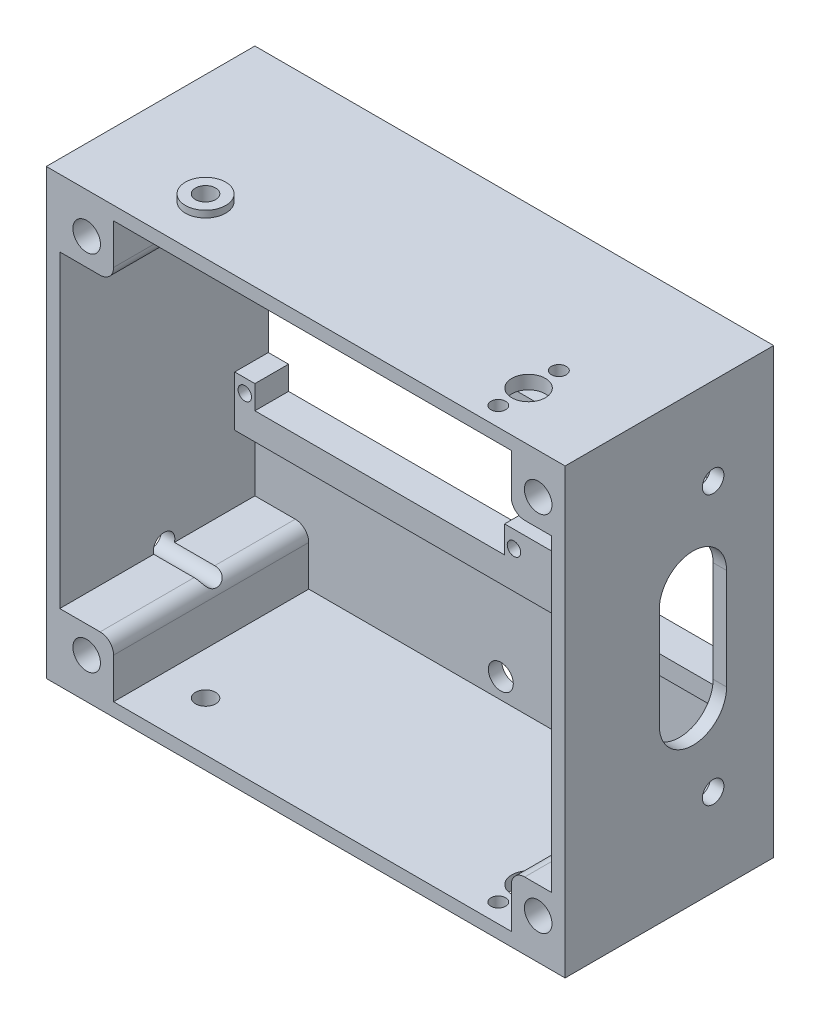
SolidWorks part; units mm, degrees
material "PET"
ref_plane "Спереди" through (0, 0, 0) normal (0, 0, 1) x (1, 0, 0)
ref_plane "Сверху" through (0, 0, 0) normal (0, 1, 0) x (1, 0, 0)
ref_plane "Справа" through (0, 0, 0) normal (1, 0, 0) x (0, 0, -1)
sketch "Эскиз1" plane through (0, 0, 0) normal (0, 0, 1) x (1, 0, 0)
  line L0 (-36.55, 30.95) -> (36.55, -30.95) construction
  line L1 (-36.55, -30.95) -> (36.55, -30.95)
  line L2 (-36.55, -30.95) -> (-36.55, 30.95)
  line L3 (-36.55, 30.95) -> (36.55, 30.95)
  line L4 (36.55, -30.95) -> (36.55, 30.95)
  line L8 (-38.55, -32.95) -> (38.55, -32.95)
  line L9 (38.55, -32.95) -> (38.55, 32.95)
  line L10 (-38.55, 32.95) -> (38.55, 32.95)
  line L11 (-38.55, -32.95) -> (-38.55, 32.95)
  point P0 (0, 0)
  dimension "D1" = 61.9
  dimension "D2" = 73.1
  dimension "D3" = 2
extrude "Бобышка-Вытянуть1" add sketch "Эскиз1" along normal blind 31
sketch "Эскиз2" plane through (0, 0, 0) normal (0, 0, -1) x (-1, 0, 0)
  line L12 (38.55, -32.95) -> (38.55, 32.95)
  line L13 (38.55, 32.95) -> (-38.55, 32.95)
  line L14 (-38.55, 32.95) -> (-38.55, -32.95)
  line L15 (-38.55, -32.95) -> (38.55, -32.95)
  line L16 (38.55, -32.95) -> (38.55, 32.95)
  line L17 (38.55, 32.95) -> (-38.55, 32.95)
  line L18 (-38.55, 32.95) -> (-38.55, -32.95)
  line L19 (-38.55, -32.95) -> (38.55, -32.95)
  dimension "D1" = 0
extrude "Бобышка-Вытянуть2" add sketch "Эскиз2" against normal blind 2
sketch "Эскиз3" plane through (0, -32.95, 0) normal (0, -1, 0) x (1, 0, 0)
  line L0 (25.8041, 19.187) -> (25.8041, 28.187) construction
  line L1 (24.9041, 19.187) -> (26.7041, 19.187) construction
  circle A0 centre (25.8041, 23.687) radius 2.5
  circle A1 centre (25.8041, 19.187) radius 1.1
  circle A2 centre (25.8041, 28.187) radius 1.1
  point P6 (25.8041, 23.687)
  dimension "D1" = 5
  dimension "D2" = 2.2
extrude "Вырез-Вытянуть1" cut sketch "Эскиз3" against normal through all both and the other way through all
sketch "Эскиз4" plane through (0, 0, 2) normal (0, 0, 1) x (1, 0, 0)
  line L0 (-36.55, 30.95) -> (-36.55, -30.95) construction
  line L1 (-36.55, -9) -> (-36.55, 9)
  line L2 (-36.55, -9) -> (13.45, -9)
  line L3 (-36.55, 9) -> (13.45, 9)
  line L4 (13.45, -9) -> (13.45, 9) construction
  line L5 (13.45, -10.2) -> (13.45, 10.2) construction
  line L6 (13.45, -10.2) -> (35.35, -10.2)
  line L7 (13.45, 10.2) -> (35.35, 10.2)
  line L8 (35.35, -10.2) -> (35.35, 10.2)
  line L9 (13.45, -10.2) -> (13.45, -9)
  line L10 (13.45, 10.2) -> (13.45, 9)
  line L11 (36.55, -30.95) -> (36.55, 30.95) construction
  circle A0 centre (0, 27.94) radius 1.651 construction
  circle A1 centre (0, -27.94) radius 1.651 construction
  circle A2 centre (0, 27.94) radius 1.651 construction
  circle A3 centre (0, -27.94) radius 1.651 construction
  circle A4 centre (0, 27.94) radius 1.851
  circle A5 centre (0, -27.94) radius 1.851
  point P10 (-36.55, 0)
  point P11 (13.45, 0)
  dimension "D2" = 50
  dimension "D3" = 18
  dimension "D4" = 1.2
  dimension "D5" = 1.2
  dimension "D1" = 0.2
extrude "Вырез-Вытянуть2" cut sketch "Эскиз4" against normal through all both and the other way through all
sketch "Эскиз5" plane through (0, 0, 2) normal (0, 0, 1) x (1, 0, 0)
  line L0 (16.3959, -10.2) -> (16.3959, 10.2)
  line L1 (16.3959, -10.2) -> (7.557, -10.2)
  line L2 (16.3959, 10.2) -> (7.557, 10.2)
  line L3 (7.557, -10.2) -> (7.557, 10.2)
  line L4 (35.35, -10.2) -> (13.45, -10.2) construction
  line L5 (13.45, 10.2) -> (35.35, 10.2) construction
  line L7 (17.0959, -7.9497) -> (17.0959, -9.7292) construction
  line L8 (7.357, -8.8303) -> (7.357, -6.3963) construction
  line L9 (-36.55, -9) -> (-33.55, -9)
  line L10 (-36.55, -9) -> (-36.55, -5.5)
  line L11 (-33.55, -9) -> (-33.55, -5.5)
  line L12 (-36.55, -5.5) -> (-33.55, -5.5)
  line L13 (13.45, -9) -> (-36.55, -9) construction
  line L14 (-36.55, 9) -> (-33.55, 9)
  line L15 (-36.55, 9) -> (-36.55, 5.5)
  line L16 (-33.55, 9) -> (-33.55, 5.5)
  line L17 (-36.55, 5.5) -> (-33.55, 5.5)
  line L18 (-36.55, 9) -> (13.45, 9) construction
  dimension "D1" = 0.7
  dimension "D2" = 0.2
  dimension "D3" = 3.5
  dimension "D4" = 3
extrude "Бобышка-Вытянуть3" add sketch "Эскиз5" against normal up to surface (2 mm away) up to face at (1.851, 27.94, 0)
sketch "Эскиз7" plane through (0, 0, 2) normal (0, 0, 1) x (1, 0, 0)
  line L0 (7.557, -5) -> (7.557, 5)
  line L1 (7.557, -5) -> (12.557, -5)
  line L2 (7.557, 5) -> (12.557, 5)
  line L3 (12.557, -5) -> (12.557, 5)
  line L4 (7.557, 9) -> (7.557, -9) construction
  point P6 (7.557, 0)
  dimension "D1" = 10
  dimension "D2" = 5
extrude "Вырез-Вытянуть3" cut sketch "Эскиз7" against normal through all both and the other way through all
sketch "Эскиз9" plane through (0, 0, 2) normal (0, 0, 1) x (1, 0, 0)
  line L20 (-36.55, 13) -> (36.55, 13)
  line L25 (-36.55, -13) -> (36.55, -13)
  line L38 (16.3959, 10.2) -> (16.3959, -10.2)
  line L39 (35.35, 10.2) -> (16.3959, 10.2)
  line L40 (35.35, -10.2) -> (35.35, 10.2)
  line L41 (16.3959, -10.2) -> (35.35, -10.2)
  line L58 (16.3959, 10.2) -> (16.3959, -10.2)
  line L59 (35.35, 10.2) -> (16.3959, 10.2)
  line L60 (35.35, -10.2) -> (35.35, 10.2)
  line L61 (16.3959, -10.2) -> (35.35, -10.2)
  line L64 (12.557, 5) -> (12.557, -5)
  line L65 (12.557, -5) -> (7.557, -5)
  line L66 (7.557, -5) -> (7.557, -9)
  line L72 (7.557, -9) -> (-33.55, -9)
  line L73 (-33.55, -9) -> (-33.55, -5.5)
  line L74 (-33.55, -5.5) -> (-36.55, -5.5)
  line L75 (-36.55, -5.5) -> (-36.55, -30.95)
  line L76 (-36.55, -30.95) -> (36.55, -30.95)
  line L80 (36.55, -30.95) -> (36.55, 30.95)
  line L98 (36.55, 30.95) -> (-36.55, 30.95)
  line L99 (-36.55, 30.95) -> (-36.55, 5.5)
  line L100 (-36.55, 5.5) -> (-33.55, 5.5)
  line L101 (-33.55, 5.5) -> (-33.55, 9)
  line L102 (-33.55, 9) -> (7.557, 9)
  line L103 (7.557, 9) -> (7.557, 5)
  line L104 (7.557, 5) -> (12.557, 5)
  line L105 (12.557, 5) -> (12.557, -5)
  line L106 (12.557, -5) -> (7.557, -5)
  line L107 (7.557, -5) -> (7.557, -9)
  line L108 (7.557, -9) -> (-33.55, -9)
  line L109 (-33.55, -9) -> (-33.55, -5.5)
  line L110 (-33.55, -5.5) -> (-36.55, -5.5)
  line L111 (-36.55, -5.5) -> (-36.55, -13)
  line L113 (36.55, -13) -> (36.55, 13)
  line L115 (-36.55, 13) -> (-36.55, 5.5)
  line L116 (-36.55, 5.5) -> (-33.55, 5.5)
  line L117 (-33.55, 5.5) -> (-33.55, 9)
  line L118 (-33.55, 9) -> (7.557, 9)
  line L119 (7.557, 9) -> (7.557, 5)
  line L120 (7.557, 5) -> (12.557, 5)
  dimension "D1" = 0
  dimension "D2" = 4
  dimension "D5" = 0
extrude "Бобышка-Вытянуть4" add sketch "Эскиз9" along normal up to surface (3 mm away)
sketch "Эскиз11" plane through (12.557, 0, 0) normal (-1, 0, 0) x (0, 0, 1)
  line L12 (5, 5) -> (0, 5)
  line L13 (0, 5) -> (0, -5)
  line L14 (0, -5) -> (5, -5)
  line L15 (5, -5) -> (5, 5)
  line L16 (5, 5) -> (0, 5)
  line L17 (0, 5) -> (0, -5)
  line L18 (0, -5) -> (5, -5)
  line L19 (5, -5) -> (5, 5)
  dimension "D1" = 0
extrude "Вырез-Вытянуть4" cut sketch "Эскиз11" against normal up to surface (3.8389 mm away) up to face at (16.3959, 0, 2.5)
sketch "Эскиз27" plane through (7.557, 0, 0) normal (-1, 0, 0) x (0, 0, 1)
  line L0 (5, -5) -> (0, -5) construction
  line L1 (0, -5) -> (0, -9) construction
  line L2 (0, -9) -> (5, -9) construction
  line L3 (5, -9) -> (5, -5) construction
  line L4 (0, 5) -> (5, 5) construction
  line L5 (5, 5) -> (5, 9) construction
  line L6 (5, 9) -> (0, 9) construction
  line L7 (0, 9) -> (0, 5) construction
  line L8 (5, -5) -> (0, -5)
  line L9 (0, -5) -> (0, -9)
  line L10 (0, -9) -> (5, -9)
  line L11 (5, -9) -> (5, -5)
  line L12 (0, 5) -> (5, 5)
  line L13 (5, 5) -> (5, 9)
  line L14 (5, 9) -> (0, 9)
  line L15 (0, 9) -> (0, 5)
extrude "Бобышка-Вытянуть12" add sketch "Эскиз27" along normal blind 5
sketch "Эскиз13" plane through (0, 0, 5) normal (0, 0, 1) x (1, 0, 0)
  line L0 (-35.05, 7.5) -> (-35.05, -7.5) construction
  line L1 (-35.05, 7.5) -> (4.95, 7.5) construction
  line L2 (-35.05, -7.5) -> (4.95, -7.5) construction
  line L3 (4.95, 7.5) -> (4.95, -7.5) construction
  line L4 (-35.05, 0) -> (-36.55, 0) construction
  line L5 (-36.55, 30.95) -> (-36.55, -30.95) construction
  circle A4 centre (-35.05, 7.5) radius 1
  circle A5 centre (-35.05, -7.5) radius 1
  circle A6 centre (4.95, -7.5) radius 1
  circle A7 centre (4.95, 7.5) radius 1
  point P0 (-35.05, 0)
  dimension "D1" = 15
  dimension "D4" = 2
  dimension "D2" = 40
  dimension "D3" = 1.5
extrude "Вырез-Вытянуть5" cut sketch "Эскиз13" against normal through all both and the other way through all
sketch "Эскиз14" plane through (0, 32.95, 0) normal (0, 1, 0) x (1, 0, 0)
  circle A0 centre (-22.1959, -23.687) radius 3
  dimension "D1" = 6
extrude "Бобышка-Вытянуть5" add sketch "Эскиз14" along normal blind 1
sketch "Эскиз15" plane through (0, -32.95, 0) normal (0, -1, 0) x (1, 0, 0)
  circle A1 centre (-22.1959, 23.687) radius 3
  circle A2 centre (-22.1959, 23.687) radius 3
  dimension "D1" = 0
extrude "Бобышка-Вытянуть6" add sketch "Эскиз15" along normal blind 1
sketch "Эскиз16" plane through (0, -33.95, 0) normal (0, -1, 0) x (1, 0, 0)
  circle A0 centre (-22.1959, 23.687) radius 1.5
  dimension "D1" = 3
extrude "Вырез-Вытянуть6" cut sketch "Эскиз16" against normal through all both and the other way through all
sketch "Эскиз18" plane through (0, 0, 2) normal (0, 0, 1) x (1, 0, 0)
  line L0 (-36.55, -30.95) -> (-28.55, -30.95)
  line L1 (-36.55, -30.95) -> (-36.55, -22.95)
  line L2 (-28.55, -30.95) -> (-28.55, -22.95)
  line L3 (-36.55, -22.95) -> (-28.55, -22.95)
  line L4 (-36.55, -30.95) -> (36.55, -30.95) construction
  line L5 (-36.55, 30.95) -> (-28.55, 30.95)
  line L6 (-36.55, 30.95) -> (-36.55, 22.95)
  line L7 (-28.55, 30.95) -> (-28.55, 22.95)
  line L8 (-36.55, 22.95) -> (-28.55, 22.95)
  line L9 (36.55, 30.95) -> (-36.55, 30.95) construction
  line L10 (36.55, 30.95) -> (36.55, 22.95)
  line L11 (36.55, 30.95) -> (28.55, 30.95)
  line L12 (36.55, 22.95) -> (28.55, 22.95)
  line L13 (28.55, 30.95) -> (28.55, 22.95)
  line L14 (36.55, -30.95) -> (36.55, 30.95) construction
  line L15 (36.55, -30.95) -> (36.55, -22.95)
  line L16 (36.55, -30.95) -> (28.55, -30.95)
  line L17 (36.55, -22.95) -> (28.55, -22.95)
  line L18 (28.55, -30.95) -> (28.55, -22.95)
  dimension "D1" = 8
  dimension "D2" = 8
extrude "Бобышка-Вытянуть9" add sketch "Эскиз18" along normal up to surface (29 mm away) up to face at (0, 0, 31)
sketch "Эскиз19" plane through (0, 0, 31) normal (0, 0, 1) x (1, 0, 0)
  line L0 (-32.55, 26.95) -> (34.55, 26.95) construction
  line L1 (34.55, 26.95) -> (34.55, -26.95) construction
  line L7 (34.55, -26.95) -> (-32.55, -26.95) construction
  line L8 (-32.55, -26.95) -> (-32.55, 26.95) construction
  line L9 (-32.55, 0) -> (0, 0) construction
  line L10 (38.55, -32.95) -> (38.55, 32.95) construction
  line L11 (38.55, 32.95) -> (-38.55, 32.95) construction
  line L12 (-38.55, 32.95) -> (-38.55, -32.95) construction
  circle A0 centre (-32.55, -26.95) radius 2.05
  circle A1 centre (-32.55, 26.95) radius 2.05
  circle A2 centre (34.55, -26.95) radius 2.05
  circle A3 centre (34.55, 26.95) radius 2.05
  dimension "D1" = 4.1
  dimension "D2" = 6
  dimension "D3" = 4
  dimension "D4" = 6
extrude "Вырез-Вытянуть7" cut sketch "Эскиз19" against normal blind 4
sketch "Эскиз20" plane through (-38.55, 0, 0) normal (-1, 0, 0) x (0, 0, 1)
  line L0 (31, 0) -> (15.5, 0) construction
  line L1 (31, 32.95) -> (31, -32.95) construction
  line L2 (15.5, 22.5) -> (15.5, -22.5) construction
  circle A0 centre (15.5, 22.5) radius 1.6
  circle A1 centre (15.5, -22.5) radius 1.6
  point P8 (15.5, 0)
  dimension "D3" = 3.2
  dimension "D1" = 15.5
  dimension "D2" = 45
extrude "Вырез-Вытянуть8" cut sketch "Эскиз20" against normal up to next and the other way through all
sketch "Эскиз21" plane through (0, 0, 0) normal (0, 0, -1) x (-1, 0, 0)
  line L0 (-38.55, 0) -> (-32.55, 0) construction
  line L1 (-38.55, -32.95) -> (-38.55, 32.95) construction
  line L2 (-32.55, 20) -> (-32.55, -20) construction
  circle A0 centre (-32.55, -20) radius 1.6
  circle A1 centre (-32.55, 20) radius 1.6
  point P7 (-32.55, 0)
  dimension "D3" = 3.2
  dimension "D1" = 6
  dimension "D2" = 40
extrude "Вырез-Вытянуть9" cut sketch "Эскиз21" against normal through all both and the other way through all
sketch "Эскиз22" plane through (38.55, 0, 0) normal (1, 0, 0) x (0, 0, -1)
  line L0 (0, 0) -> (-9, 0) construction
  line L1 (0, -32.95) -> (0, 32.95) construction
  line L2 (-9, -20) -> (-9, 20) construction
  circle A0 centre (-9, 20) radius 1.6
  circle A1 centre (-9, -20) radius 1.6
  point P7 (-9, 0)
  dimension "D3" = 3.2
  dimension "D1" = 9
  dimension "D2" = 40
extrude "Вырез-Вытянуть10" cut sketch "Эскиз22" against normal up to next
sketch "Эскиз28" plane through (28.55, 0, 0) normal (-1, 0, 0) x (0, 0, 1)
  line L20 (2, 22.95) -> (31, 22.95) construction
  line L21 (31, 22.95) -> (31, 30.95) construction
  line L22 (31, 30.95) -> (2, 30.95) construction
  line L23 (2, 30.95) -> (2, 22.95) construction
  line L24 (2, -30.95) -> (31, -30.95) construction
  line L25 (31, -30.95) -> (31, -22.95) construction
  line L26 (31, -22.95) -> (2, -22.95) construction
  line L27 (2, -22.95) -> (2, -30.95) construction
  line L28 (2, 22.95) -> (31, 22.95)
  line L29 (31, 22.95) -> (31, 30.95)
  line L30 (31, 30.95) -> (2, 30.95)
  line L31 (2, 30.95) -> (2, 22.95)
  line L32 (2, -30.95) -> (31, -30.95)
  line L33 (31, -30.95) -> (31, -22.95)
  line L34 (31, -22.95) -> (2, -22.95)
  line L35 (2, -22.95) -> (2, -30.95)
extrude "Вырез-Вытянуть13" cut sketch "Эскиз28" against normal blind 2
fillet "Скругление1" radius 2 6 edges at (-28.55, -22.95, 24.0177) (-28.55, -22.95, 7.9823) (-28.55, 22.95, 7.9823) (-28.55, 22.95, 24.0177) (30.55, -22.95, 16.5) (30.55, 22.95, 16.5)
sketch "Эскиз26" plane through (38.55, 0, 0) normal (1, 0, 0) x (0, 0, -1)
  line L0 (0, 0) -> (-12, 0) construction
  line L1 (-12, 7.5) -> (-12, -7.5) construction
  line L2 (-7, 7.5) -> (-7, -7.5)
  line L3 (-17, 7.5) -> (-17, -7.5)
  arc A0 (-7, 7.5) -> (-17, 7.5) centre (-12, 7.5) ccw
  arc A1 (-17, -7.5) -> (-7, -7.5) centre (-12, -7.5) ccw
  point P5 (-12, 0)
  dimension "D3" = 5
  dimension "D1" = 12
  dimension "D2" = 15
extrude "Вырез-Вытянуть12" cut sketch "Эскиз26" against normal up to next
sketch "Эскиз29" plane through (2.557, 0, 0) normal (-1, 0, 0) x (0, 0, 1)
  line L4 (0, 9) -> (0, 5)
  line L5 (0, 5) -> (5, 5)
  line L6 (5, 5) -> (5, 9)
  line L7 (5, 9) -> (0, 9)
  line L8 (0, 9) -> (0, 5)
  line L9 (0, 5) -> (5, 5)
  line L10 (5, 5) -> (5, 9)
  line L11 (5, 9) -> (0, 9)
  line L12 (5, -9) -> (5, -5)
  line L13 (5, -5) -> (0, -5)
  line L14 (0, -5) -> (0, -9)
  line L15 (0, -9) -> (5, -9)
  line L16 (5, -9) -> (5, -5)
  line L17 (5, -5) -> (0, -5)
  line L18 (0, -5) -> (0, -9)
  line L19 (0, -9) -> (5, -9)
  dimension "D1" = 0
  dimension "D2" = 0
extrude "Вырез-Вытянуть14" cut sketch "Эскиз29" against normal blind 1
